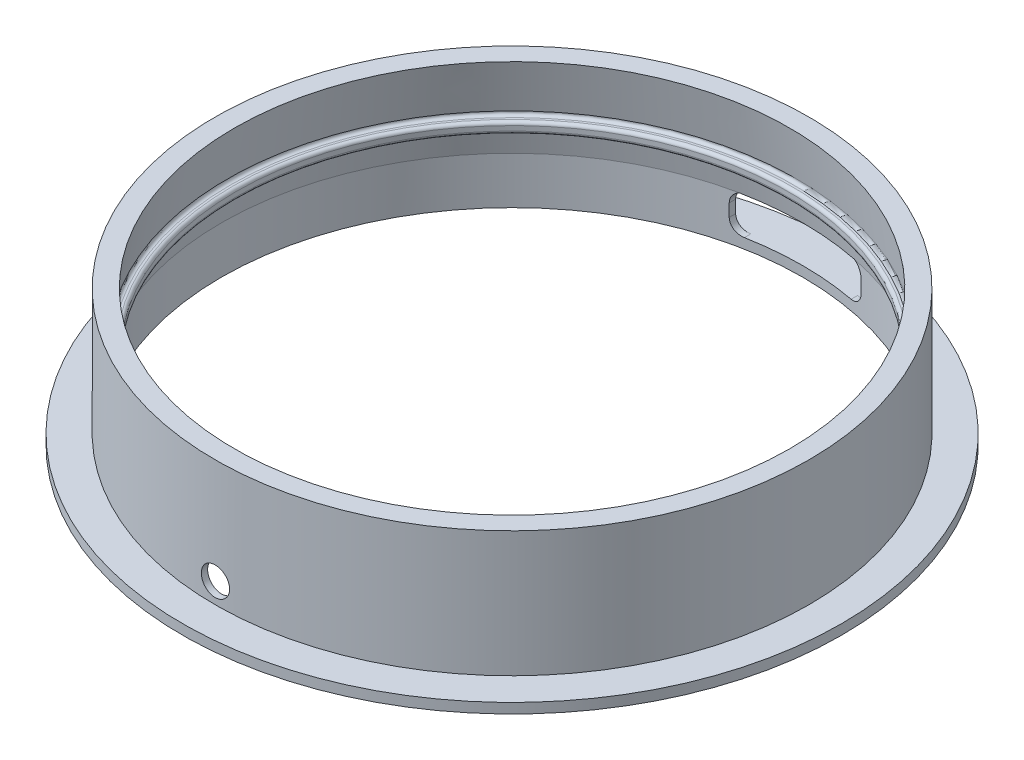
SolidWorks part; units mm, degrees
ref_plane "Front Plane" through (0, 0, 0) normal (0, 0, 1) x (1, 0, 0)
ref_plane "Top Plane" through (0, 0, 0) normal (0, 1, 0) x (1, 0, 0)
ref_plane "Right Plane" through (0, 0, 0) normal (1, 0, 0) x (0, 0, -1)
sketch "Sketch2" plane through (0, 0, 0) normal (0, 0, 1) x (1, 0, 0)
  line L0 (46.3, 0) -> (46.3, 21.6)
  line L1 (46.3, 21.6) -> (47.3, 21.6)
  line L2 (47.3, 21.6) -> (47.3, 1.6)
  line L3 (47.3, 1.6) -> (52.5, 1.6)
  line L4 (52.5, 1.6) -> (52.5, 0)
  line L5 (52.5, 0) -> (46.3, 0)
  line L6 (0, -1000) -> (0, 49000) construction
  dimension "D1" = 52.5
  dimension "D2" = 46.3
  dimension "D3" = 20
  dimension "D4" = 1.6
  dimension "D5" = 1
revolve "Revolve1" add sketch "Sketch2" angle 360 about L6
sketch "Sketch4" plane through (0, 0, 0) normal (0, 0, 1) x (1, 0, 0)
  line L1 (-10.5, 7.6) -> (10.5, 7.6)
  line L2 (-10.5, 7.6) -> (-10.5, 1.6)
  line L3 (-10.5, 1.6) -> (10.5, 1.6)
  line L4 (10.5, 7.6) -> (10.5, 1.6)
  line L5 (-10.5, 7.6) -> (10.5, 1.6) construction
  line L6 (-10.5, 1.6) -> (10.5, 7.6) construction
  line L7 (52.5, 1.6) -> (-52.5, 1.6) construction
  point P0 (0, 4.6)
  dimension "D1" = 21
  dimension "D2" = 6
extrude "Cut-Extrude1" cut sketch "Sketch4" against normal up to next
fillet "Fillet1" radius 2 4 edges at (10.5, 1.6, -45.6068) (10.5, 7.6, -45.6068) (-10.5, 7.6, -45.6068) (-10.5, 1.6, -45.6068)
sketch "Sketch5" plane through (0, 0, 0) normal (0, 0, 1) x (1, 0, 0)
  line L0 (52.5, 1.6) -> (-52.5, 1.6) construction
  circle A0 centre (0, 4.85) radius 2.25
  dimension "D1" = 4.5
  dimension "D2" = 3.25
extrude "Cut-Extrude2" cut sketch "Sketch5" along normal up to next
sketch "Sketch6" plane through (0, 0, 0) normal (0, 0, 1) x (1, 0, 0)
  line L0 (-46.3, 21.6) -> (-46.3, 7.5)
  line L1 (-46.3, 7.5) -> (-44.243, 21.6)
  line L2 (-44.243, 21.6) -> (-46.3, 21.6)
  line L3 (-46.3, 0) -> (46.3, 0) construction
  line L4 (-45.6873, 11.7) -> (-44, 11.7)
  line L5 (-44, 11.7) -> (-44, 13.45)
  line L6 (-44, 13.45) -> (-45.432, 13.45)
  line L7 (0, -1000) -> (0, 49000) construction
  dimension "D1" = 7.5
  dimension "D2" = 8.3
  dimension "D3" = 4.2
  dimension "D4" = 1.75
  dimension "D5" = 44
revolve "Revolve2" add sketch "Sketch6" angle 360 about L7 region at (-45.6143, 16.9, 0) region at (-44.7816, 12.5511, 0)
fillet "Fillet2" radius 0.5 4 edges at (45.6873, 11.7, 0) (44, 11.7, 0) (45.432, 13.45, 0) (44, 13.45, 0)
